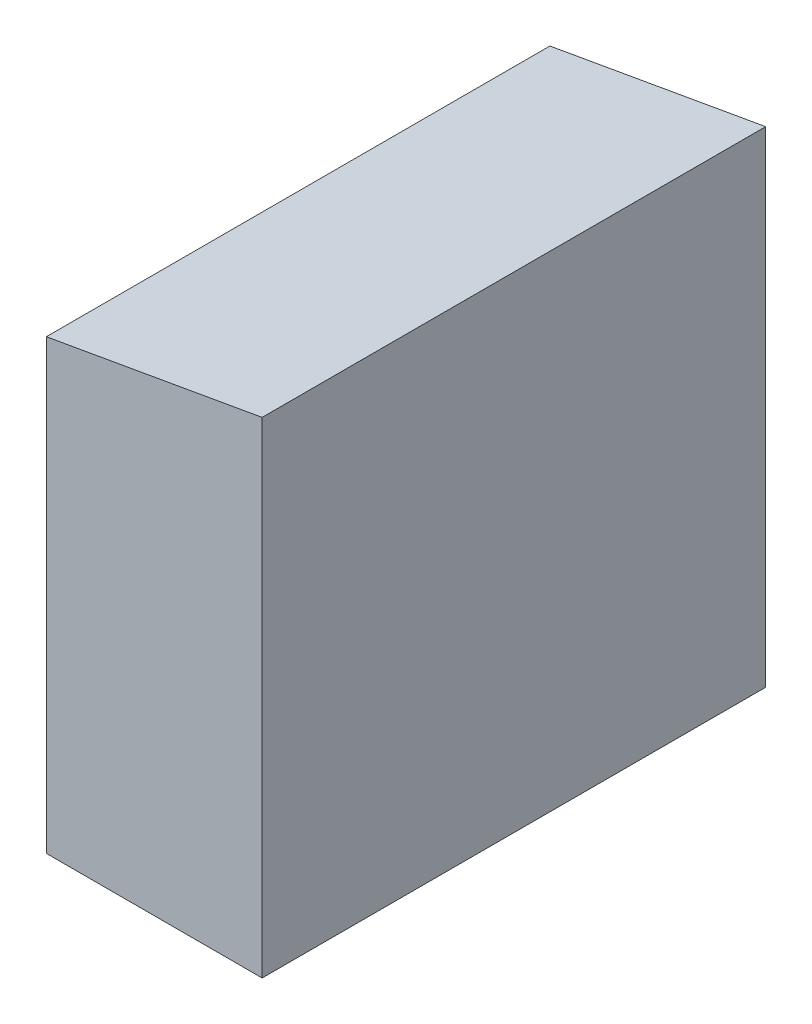
SolidWorks part; units mm, degrees
material "SPF Select 2Btr Grade Lumber"
ref_plane "Front Plane" through (0, 0, 0) normal (0, 0, 1) x (1, 0, 0)
ref_plane "Top Plane" through (0, 0, 0) normal (0, 1, 0) x (1, 0, 0)
ref_plane "Right Plane" through (0, 0, 0) normal (1, 0, 0) x (0, 0, -1)
sketch "Sketch2" plane through (0, 0, 0) normal (0, 0, 1) x (1, 0, 0)
  line L0 (38.1, 85.7181) -> (0, 79)
  line L1 (0, 0) -> (38.1, 0)
  line L2 (0, 0) -> (0, 79)
  line L4 (38.1, 0) -> (38.1, 85.7181)
  dimension "D1" = 38.1
  dimension "D2" = 80
  dimension "D3" = 79
extrude "Boss-Extrude1" add sketch "Sketch2" along normal blind 88.9
